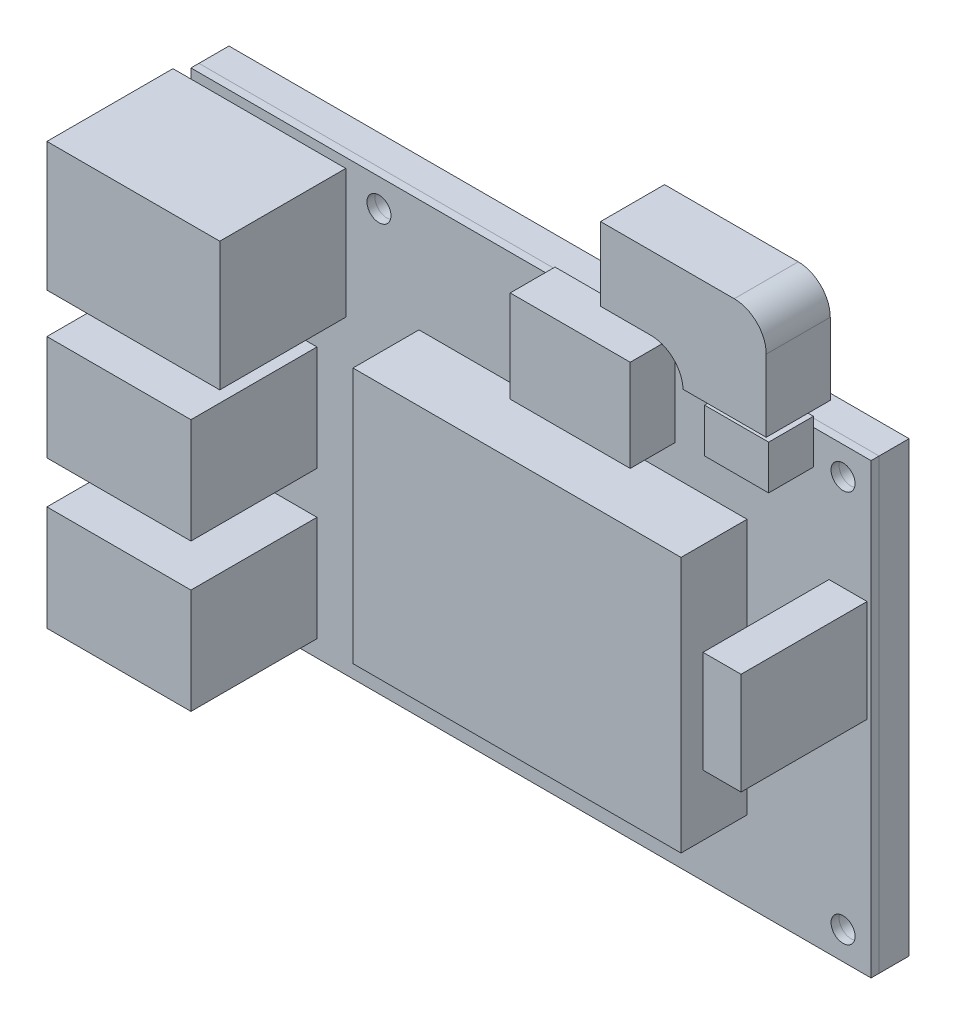
SolidWorks part; units mm, degrees
ref_plane "Front Plane" through (0, 0, 0) normal (0, 0, 1) x (1, 0, 0)
ref_plane "Top Plane" through (0, 0, 0) normal (0, 1, 0) x (1, 0, 0)
ref_plane "Right Plane" through (0, 0, 0) normal (1, 0, 0) x (0, 0, -1)
sketch "Sketch1" plane through (0, 0, 0) normal (0, 0, 1) x (1, 0, 0)
  line L0 (-19, 24.5) -> (39, 24.5) construction
  line L1 (-42.5, 28) -> (42.5, 28)
  line L2 (-42.5, 28) -> (-42.5, -28)
  line L3 (-42.5, -28) -> (42.5, -28)
  line L4 (42.5, 28) -> (42.5, -28)
  line L5 (39, 24.5) -> (39, -24.5) construction
  line L6 (39, -24.5) -> (-19, -24.5) construction
  line L7 (-19, -24.5) -> (-19, 24.5) construction
  line L8 (39, 0) -> (42.5, 0) construction
  line L9 (55, 0) -> (-55, 0) construction
  line L10 (0, -55) -> (0, 55) construction
  circle A0 centre (-19, 24.5) radius 1.5
  circle A1 centre (-19, -24.5) radius 1.5
  circle A2 centre (39, 24.5) radius 1.5
  circle A3 centre (39, -24.5) radius 1.5
  point P12 (-19, 0)
  point P17 (0, 28)
  dimension "D1" = 3
  dimension "D2" = 58
  dimension "D3" = 49
  dimension "D4" = 56
  dimension "D5" = 85
  dimension "D6" = 3.5
extrude "Boss-Extrude1" add sketch "Sketch1" along normal blind 1
extrude "Boss-Extrude2" add sketch "Sketch1<2>" against normal blind 3.75 separate body
sketch "Sketch1<2>" plane through (0, 0, 0) normal (0, 0, 1) x (1, 0, 0) same geometry as "Sketch1"
sketch "Sketch3" plane through (0, 0, 1) normal (0, 0, 1) x (1, 0, 0)
  line L0 (42.5, 28) -> (42.5, -28) construction
  line L1 (-14, 13.9) -> (27, 13.9)
  line L2 (-14, 13.9) -> (-14, -18.1)
  line L3 (-14, -18.1) -> (27, -18.1)
  line L4 (27, 13.9) -> (27, -18.1)
  line L5 (-42.5, 28) -> (42.5, 28) construction
  dimension "D1" = 41
  dimension "D2" = 32
  dimension "D3" = 15.5
  dimension "D4" = 14.1
extrude "Boss-Extrude3" add sketch "Sketch3" along normal blind 8.25
sketch "Sketch4" plane through (0, 0, 1) normal (0, 0, 1) x (1, 0, 0)
  line L0 (-44.7495, -0.89) -> (-34.7495, -0.89) construction
  line L1 (-44.7495, 5.68) -> (-26.7495, 5.68)
  line L2 (-44.7495, 5.68) -> (-44.7495, -7.46)
  line L3 (-44.7495, -7.46) -> (-26.7495, -7.46)
  line L4 (-26.7495, 5.68) -> (-26.7495, -7.46)
  line L5 (-44.7495, -12.76) -> (-26.7495, -12.76)
  line L6 (-44.7495, -12.76) -> (-44.7495, -25.9)
  line L7 (-44.7495, -25.9) -> (-26.7495, -25.9)
  line L8 (-26.7495, -12.76) -> (-26.7495, -25.9)
  line L9 (-44.7495, -19.33) -> (-34.7495, -19.33) construction
  line L10 (42.5, -28) -> (42.5, 28) construction
  line L11 (37.245, 12.5) -> (42, 12.5)
  line L12 (-44.7495, 26.8) -> (-23.1495, 26.8)
  line L13 (-44.7495, 26.8) -> (-44.7495, 10.7)
  line L14 (-44.7495, 10.7) -> (-23.1495, 10.7)
  line L15 (-23.1495, 26.8) -> (-23.1495, 10.7)
  line L16 (37.245, 12.5) -> (37.245, -0.25)
  line L17 (37.245, -0.25) -> (42, -0.25)
  line L18 (42, 12.5) -> (42, -0.25)
  line L19 (42.5, 28) -> (-42.5, 28) construction
  dimension "D1" = 18
  dimension "D2" = 13.14
  dimension "D3" = 10
  dimension "D4" = 5.3
  dimension "D5" = 2.1
  dimension "D6" = 21.6
  dimension "D7" = 1.2
  dimension "D8" = 16.1
  dimension "D9" = 4.755
  dimension "D10" = 12.75
  dimension "D11" = 0.5
  dimension "D12" = 15.5
extrude "Boss-Extrude4" add sketch "Sketch4" along normal blind 15.75
sketch "Sketch5" plane through (0, 0, 1) normal (0, 0, 1) x (1, 0, 0)
  line L1 (3, 29.2) -> (18, 29.2)
  line L2 (3, 29.2) -> (3, 17.7)
  line L3 (3, 17.7) -> (18, 17.7)
  line L4 (18, 29.2) -> (18, 17.7)
  line L5 (27.3, 29.2) -> (35.3, 29.2)
  line L6 (27.3, 29.2) -> (27.3, 23.7)
  line L7 (27.3, 23.7) -> (35.3, 23.7)
  line L8 (35.3, 29.2) -> (35.3, 23.7)
  dimension "D1" = 15
  dimension "D2" = 8
  dimension "D3" = 11.5
  dimension "D4" = 5.5
  dimension "D5" = 1.2
  dimension "D6" = 24.5
  dimension "D7" = 7.2
extrude "Boss-Extrude5" add sketch "Sketch5" along normal blind 5.6
sketch "Sketch6" plane through (0, 0, 0) normal (0, 0, 1) x (1, 0, 0)
  line L0 (-42.5, -28) -> (42.5, -28) construction
  line L1 (-0.5969, -28.5) -> (-12.2069, -28.5)
  line L2 (-0.5969, -28.5) -> (-0.5969, -12.75)
  line L3 (-0.5969, -12.75) -> (-12.2069, -12.75)
  line L4 (-12.2069, -28.5) -> (-12.2069, -12.75)
  dimension "D1" = 11.61
  dimension "D2" = 15.75
  dimension "D3" = 0.5
extrude "Boss-Extrude6" add sketch "Sketch6" against normal blind 4 separate body
sketch "Sketch7" plane through (0, 0, 0) normal (0, 0, 1) x (1, 0, 0)
  line L0 (36.3996, 30.9696) -> (36.3996, 43.9696)
  line L1 (36.3996, 43.9696) -> (15.6906, 43.9696)
  line L2 (15.6906, 43.9696) -> (15.6906, 34.7989)
  line L3 (15.6906, 34.7989) -> (26.0068, 34.7989)
  line L4 (26.0068, 34.7989) -> (26.0068, 30.9696)
  line L5 (26.0068, 30.9696) -> (36.3996, 30.9696)
  dimension "D1" = 13
extrude "Boss-Extrude7" add sketch "Sketch7" along normal blind 8 separate body
fillet "Fillet1" radius 4 2 edges at (36.3996, 43.9696, 4) (26.0068, 34.7989, 4)
